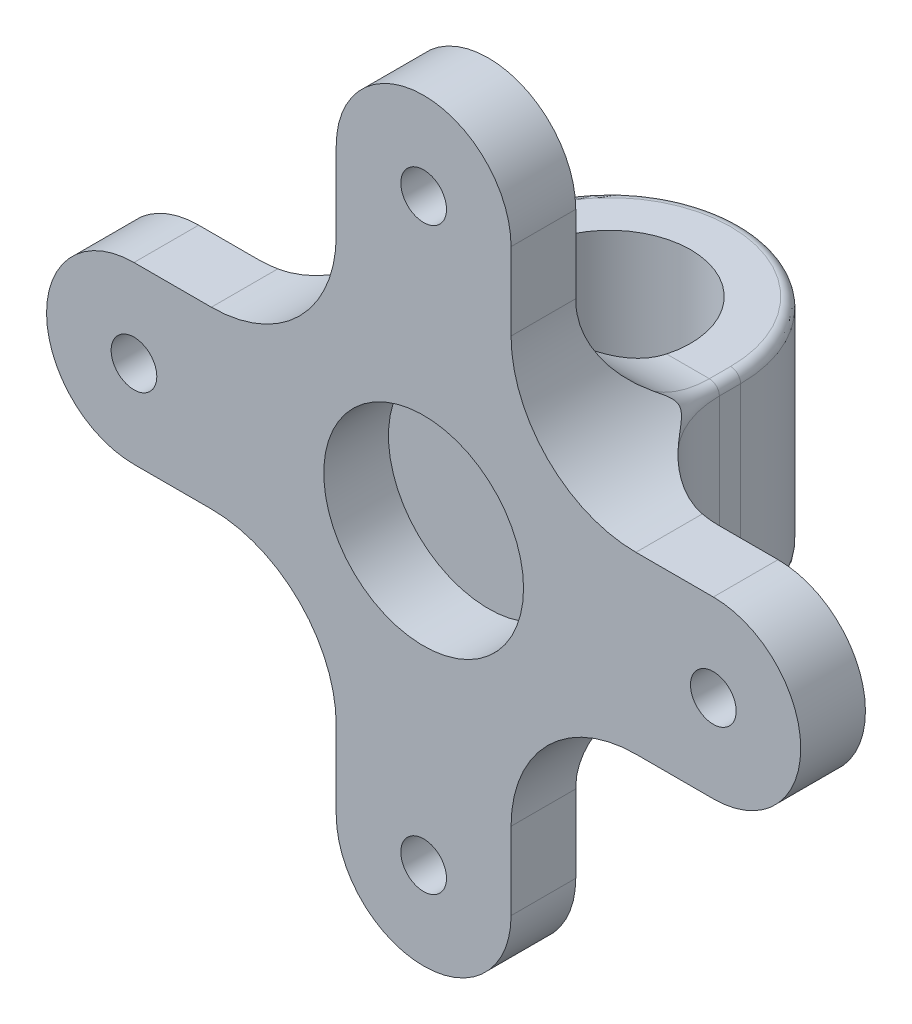
SolidWorks part; units mm, degrees
material "ABS"
ref_plane "Front Plane" through (0, 0, 0) normal (0, 0, 1) x (1, 0, 0)
ref_plane "Top Plane" through (0, 0, 0) normal (0, 1, 0) x (1, 0, 0)
ref_plane "Right Plane" through (0, 0, 0) normal (1, 0, 0) x (0, 0, -1)
sketch "Sketch1" plane through (0, 0, 0) normal (0, 0, 1) x (1, 0, 0)
  line L0 (-8.75, 29) -> (-8.75, 8.75)
  line L1 (8.75, 29) -> (8.75, 8.75)
  line L2 (29, 8.75) -> (8.75, 8.75)
  line L3 (29, -8.75) -> (8.75, -8.75)
  line L4 (8.75, -29) -> (8.75, -8.75)
  line L5 (-8.75, -29) -> (-8.75, -8.75)
  line L6 (-29, -8.75) -> (-8.75, -8.75)
  line L7 (-29, 8.75) -> (-8.75, 8.75)
  circle A0 centre (0, 0) radius 12 construction
  circle A1 centre (0, 0) radius 10
  circle A4 centre (0, 29) radius 2.286
  arc A5 (8.75, 29) -> (-8.75, 29) centre (0, 29) ccw
  arc A6 (29, -8.75) -> (29, 8.75) centre (29, 0) ccw
  circle A7 centre (29, 0) radius 2.286
  arc A8 (-8.75, -29) -> (8.75, -29) centre (0, -29) ccw
  circle A9 centre (0, -29) radius 2.286
  arc A10 (-29, 8.75) -> (-29, -8.75) centre (-29, 0) ccw
  circle A11 centre (-29, 0) radius 2.286
  point P38 (0, 0)
  point P40 (0, 0)
  dimension "D1" = 24
  dimension "D2" = 20
  dimension "D6" = 4.572
  dimension "D4" = 17.5
  dimension "D7" = 29
  dimension "D9" = 4
extrude "Boss-Extrude1" add sketch "Sketch1" along normal blind 6.477
sketch "Sketch3" plane through (0, 0, 0) normal (0, 0, -1) x (-1, 0, 0)
  line L0 (26.9103, -3.6195) -> (31.0897, -3.6195)
  line L1 (3.6195, 26.9103) -> (3.6195, 31.0897)
  line L2 (3.6195, 31.0897) -> (0, 33.1794)
  line L3 (0, 33.1794) -> (-3.6195, 31.0897)
  line L4 (-3.6195, 31.0897) -> (-3.6195, 26.9103)
  line L5 (-3.6195, 26.9103) -> (0, 24.8206)
  line L6 (0, 24.8206) -> (3.6195, 26.9103)
  line L7 (31.0897, -3.6195) -> (33.1794, 0)
  line L8 (33.1794, 0) -> (31.0897, 3.6195)
  line L9 (31.0897, 3.6195) -> (26.9103, 3.6195)
  line L10 (26.9103, 3.6195) -> (24.8206, 0)
  line L11 (24.8206, 0) -> (26.9103, -3.6195)
  line L12 (-3.6195, -26.9103) -> (-3.6195, -31.0897)
  line L13 (-3.6195, -31.0897) -> (0, -33.1794)
  line L14 (0, -33.1794) -> (3.6195, -31.0897)
  line L15 (3.6195, -31.0897) -> (3.6195, -26.9103)
  line L16 (3.6195, -26.9103) -> (0, -24.8206)
  line L17 (0, -24.8206) -> (-3.6195, -26.9103)
  line L18 (-26.9103, 3.6195) -> (-31.0897, 3.6195)
  line L19 (-31.0897, 3.6195) -> (-33.1794, 0)
  line L20 (-33.1794, 0) -> (-31.0897, -3.6195)
  line L21 (-31.0897, -3.6195) -> (-26.9103, -3.6195)
  line L22 (-26.9103, -3.6195) -> (-24.8206, 0)
  line L23 (-24.8206, 0) -> (-26.9103, 3.6195)
  circle A0 centre (0, 29) radius 3.6195 construction
  point P31 (0, 0)
  dimension "D1" = 7.239
  dimension "D2" = 4
extrude "Cut-Extrude1" cut sketch "Sketch3" against normal blind 3.2385
fillet "Fillet15" radius 12.5 4 edges at (8.75, -8.75, 3.2385) (-8.75, -8.75, 3.2385) (-8.75, 8.75, 3.2385) (8.75, 8.75, 3.2385)
sketch "Sketch2" plane through (0, 0, 0) normal (0, 0, -1) x (-1, 0, 0)
  circle A0 centre (0, 0) radius 12.625
  circle A1 centre (0, 0) radius 17.5
  dimension "D1" = 25.25
  dimension "D2" = 35
sketch "Sketch4" plane through (0, 0, 0) normal (0, 1, 0) x (1, 0, 0)
  line L0 (-13.125, 0) -> (-13.125, 12.125)
  line L1 (-8.75, 0) -> (-21.25, 0) construction
  line L2 (13.125, 12.125) -> (13.125, 0)
  line L3 (21.25, 0) -> (8.75, 0) construction
  line L4 (-13.125, 0) -> (13.125, 0)
  arc A0 (-13.125, 12.125) -> (13.125, 12.125) centre (0, 12.125) cw
  circle A1 centre (0, 12.125) radius 8.125
  point P11 (0, 4)
  dimension "D1" = 16.25
  dimension "D2" = 5
  dimension "D3" = 4
  dimension "D4" = 26.25
extrude "Boss-Extrude2" add sketch "Sketch4" along normal mid plane 22
fillet "Fillet17" radius 1 6 edges at (13.125, 11, -6.0625) (-13.125, 11, -6.0625) (-13.125, -11, -6.0625) (0, -11, -25.25) (0, 11, -25.25) (13.125, -11, -6.0625)
fillet "Fillet18" radius 10 4 edges at (-13.125, 0, 0) (0, 11, 0) (13.125, 0, 0) (0, -11, 0)
